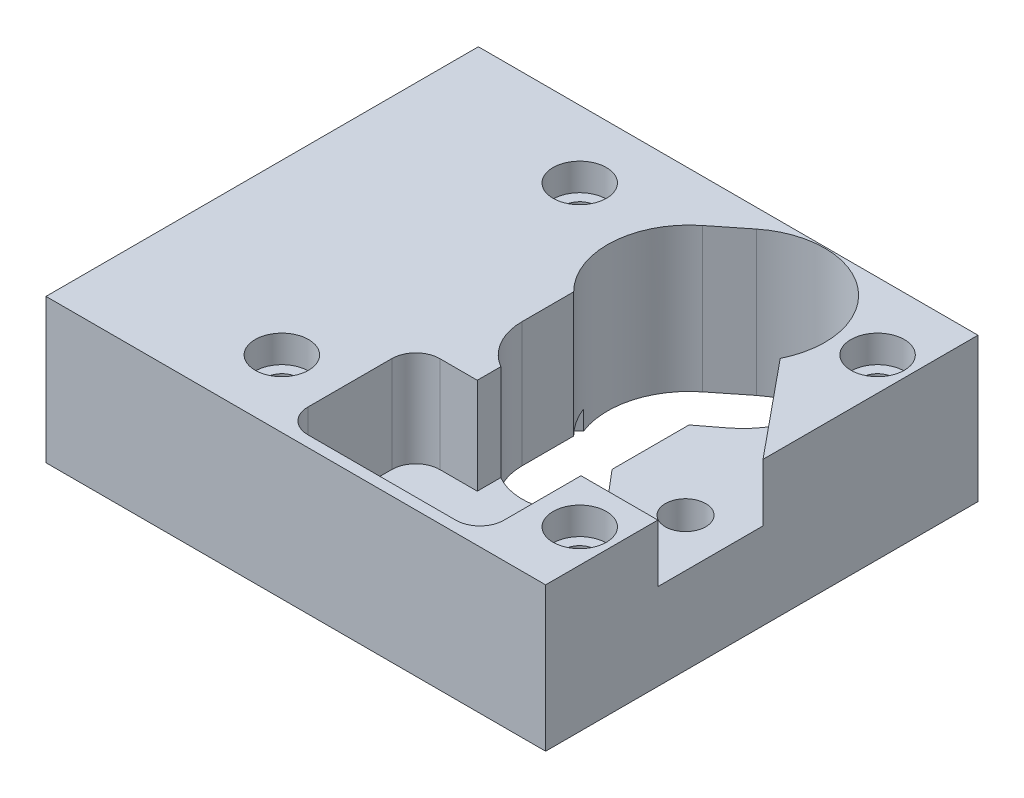
SolidWorks part; units mm, degrees
ref_plane "Front Plane" through (0, 0, 0) normal (0, 0, 1) x (1, 0, 0)
ref_plane "Top Plane" through (0, 0, 0) normal (0, 1, 0) x (1, 0, 0)
ref_plane "Right Plane" through (0, 0, 0) normal (1, 0, 0) x (0, 0, -1)
sketch "Sketch1" plane through (0, 0, 0) normal (0, 1, 0) x (1, 0, 0)
  line L1 (0, 0) -> (52, 0)
  line L2 (0, 0) -> (0, 45)
  line L3 (0, 45) -> (52, 45)
  line L4 (52, 0) -> (52, 45)
  dimension "D1" = 52
  dimension "D2" = 45
extrude "Boss-Extrude1" add sketch "Sketch1" along normal blind 15
sketch "Sketch2" plane through (0, 0, 0) normal (0, -1, 0) x (1, 0, 0)
  line L0 (33.0489, 0) -> (33.0489, -45) construction
  line L3 (52, -22.5) -> (0, -22.5) construction
  line L4 (52, 0) -> (52, -45) construction
  line L5 (0, -45) -> (0, 0) construction
  circle A0 centre (33.0489, -22.5) radius 11.5
  point P14 (17.5489, -7)
  point P15 (48.5489, -7)
  point P16 (48.5489, -38)
  point P17 (17.5489, -38)
  dimension "D1" = 23
  dimension "D2" = 15.5
  dimension "D3" = 15.5
extrude "Cut-Extrude1" cut sketch "Sketch2" against normal blind 2
ref_axis "Axis1" through (33.0489, 20.8863, -22.5) along (0, -1, 0)
hole_wizard "CBORE for #4 Socket Head Cap Screw1" positions "Sketch4" profile "Sketch5" counterbore size "#4" standard "Ansi Inch" end condition through all
sketch "Sketch4" plane through (0, 15, 0) normal (0, 1, 0) x (-1, 0, 0)
  point P0 (-48.5489, -38)
  point P1 (-48.5489, -7)
  point P3 (-17.5489, -7)
  point P5 (-17.5489, -38)
  dimension "D1" = 31
  dimension "D2" = 31
  dimension "D3" = 15.5
  dimension "D4" = 15.5
sketch "Sketch5" plane through (48.5489, 15, -38) normal (1, 0, 0) x (0, 0, 1)
  line L0 (0, 0) -> (0, 15)
  line L1 (0, 15) -> (1.6319, 15)
  line L3 (1.6319, 15) -> (1.632, 2.8448)
  line L4 (1.632, 2.8448) -> (2.7788, 2.8448)
  line L5 (2.7788, 2.8448) -> (2.7788, 0)
  line L7 (2.7788, 0) -> (0, 0)
  line L11 (0, -6.35) -> (0, 107.95) construction
  dimension "Thru Hole Dia." = 3.2639
  dimension "Thru Hole Depth" = 15
  dimension "C'Bore Dia." = 5.5575
  dimension "C'Bore Depth" = 2.8448
sketch "Layout sketch" plane through (0, 15, 0) normal (0, 1, 0) x (-1, 0, 0)
  line L0 (-5.4445, -22.5) -> (-55.1458, -22.5) construction
  line L1 (-33.0489, -33.89) -> (-47, -19.5594) construction
  line L2 (-52, 0) -> (-52, -45) construction
  line L3 (11.3783, -26.5) -> (-64.4521, -26.5) construction
  line L4 (-27.0489, -27.8692) -> (-27.0489, -22.5) construction
  line L6 (-39.0489, -22.5) -> (-39.0489, -27.8692) construction
  line L7 (-27.7584, -40.5429) -> (-30.8892, -43.0325) construction
  line L8 (-39.0489, -27.8692) -> (-41.3505, -29.6334) construction
  circle A0 centre (-33.0489, -22.5) radius 4 construction
  circle A1 centre (-33.0489, -33.89) radius 6.5 construction
  circle A2 centre (-47, -19.5594) radius 2.5 construction
  circle A3 centre (-33.0489, -33.89) radius 2.5 construction
  arc A4 (-27.0489, -27.8692) -> (-27.7584, -40.5429) centre (-33.0489, -33.89) cw construction
  arc A5 (-27.0489, -22.5) -> (-39.0489, -22.5) centre (-33.0489, -22.5) ccw construction
  arc A6 (-33.0489, -33.89) -> (-48.625, -39.4933) centre (-47, -19.5594) cw construction
  arc A7 (-30.8892, -43.0325) -> (-41.3505, -29.6334) centre (-36.1796, -36.3796) cw construction
  dimension "D1" = 8
  dimension "D2" = 13
  dimension "D3" = 5
  dimension "D4" = 5
  dimension "D5" = 2
  dimension "D6" = 2
  dimension "D8" = 2
  dimension "D7" = 2
  dimension "D10" = 20
  dimension "D12" = 0.89
  dimension "D9" = 4
  dimension "D11" = 5
sketch "Arm sketch" plane through (0, 15, 0) normal (0, 1, 0) x (1, 0, 0)
  line L0 (36.7672, 37.2328) -> (50.6672, 21.7711)
  line L3 (36.6105, 14.8843) -> (36.6105, 2.8045)
  line L4 (36.6105, 2.8045) -> (39.1105, 2.8045)
  line L5 (41.6105, 5.3045) -> (41.6105, 11.4363)
  line L6 (44.1105, 13.9363) -> (52.5715, 13.9363)
  line L7 (55.0562, 11.7121) -> (56.318, 0.3453)
  line L8 (56.318, 0.3453) -> (61.318, 0.3453)
  line L9 (61.318, 0.3453) -> (61.318, 15.5735)
  arc A0 (36.7672, 37.2328) -> (33.3407, 28.8985) centre (33.0489, 33.89) ccw
  arc A1 (33.3407, 28.8985) -> (36.6105, 14.8843) centre (33.7412, 21.6034) cw
  arc A2 (39.1105, 2.8045) -> (41.6105, 5.3045) centre (39.1105, 5.3045) ccw
  arc A3 (44.1105, 13.9363) -> (41.6105, 11.4363) centre (44.1105, 11.4363) ccw
  arc A4 (52.5715, 13.9363) -> (55.0562, 11.7121) centre (52.5715, 11.4363) cw
  arc A5 (50.6672, 21.7711) -> (58.8449, 18.0733) centre (58.9653, 29.231) ccw
  arc A6 (58.8449, 18.0733) -> (61.318, 15.5735) centre (58.818, 15.5735) cw
  dimension "D2" = 5
  dimension "D3" = 2.5
  dimension "D4" = 2.5
  dimension "D5" = 2.5
  dimension "D6" = 2.5
  dimension "D8" = 11.1583
  dimension "D1" = 5
  dimension "D7" = 5
sketch "Sketch8" plane through (0, 15, 0) normal (0, 1, 0) x (1, 0, 0)
  line L0 (27.0489, 22.5) -> (27.0489, 27.8692)
  line L1 (27.7584, 40.5429) -> (30.8892, 43.0325)
  line L2 (41.3505, 29.6334) -> (39.0489, 27.8692)
  line L3 (39.0489, 27.8692) -> (39.0489, 22.5)
  arc A0 (39.0489, 22.5) -> (27.0489, 22.5) centre (33.0489, 22.5) cw
  arc A1 (30.8892, 43.0325) -> (41.3505, 29.6334) centre (36.1796, 36.3796) cw
  arc A2 (27.7584, 40.5429) -> (27.0489, 27.8692) centre (33.0489, 33.89) ccw
extrude "Cut-Extrude3" cut sketch "Sketch8" against normal through all
sketch "Sketch11" plane through (0, 15, 0) normal (0, 1, 0) x (1, 0, 0)
  line L0 (23.6015, 12.3843) -> (23.6015, 3.6525)
  line L1 (26.1015, 1.1525) -> (41.5055, 1.1525)
  line L2 (44.0055, 3.6525) -> (44.0055, 13.0932)
  line L4 (39.0489, 19.863) -> (39.0489, 34.7253)
  line L7 (39.0489, 34.7253) -> (27.0489, 34.7253)
  line L8 (27.0489, 34.7253) -> (27.0489, 22.5)
  line L9 (26.1015, 14.8843) -> (30.0028, 14.8843)
  line L10 (30.0028, 14.8843) -> (30.0028, 17.3307)
  line L12 (39.0489, 22.5) -> (39.0489, 27.8692) construction
  line L13 (43.4134, 14.7087) -> (39.0489, 19.863)
  arc A1 (27.0489, 22.5) -> (30.0028, 17.3307) centre (33.0489, 22.5) ccw
  arc A2 (41.5055, 1.1525) -> (44.0055, 3.6525) centre (41.5055, 3.6525) ccw
  arc A3 (27.0489, 22.5) -> (39.0489, 22.5) centre (33.0489, 22.5) ccw construction
  arc A4 (23.6015, 3.6525) -> (26.1015, 1.1525) centre (26.1015, 3.6525) ccw
  arc A5 (23.6015, 12.3843) -> (26.1015, 14.8843) centre (26.1015, 12.3843) cw
  arc A6 (44.0055, 13.0932) -> (43.4134, 14.7087) centre (41.5055, 13.0932) ccw
  dimension "D1" = 2.5
  dimension "D2" = 2.5
  dimension "D3" = 2.5
  dimension "D4" = 2.5
extrude "Cut-Extrude4" cut sketch "Sketch11" against normal blind 10
sketch "Sketch12" plane through (0, 15, 0) normal (0, 1, 0) x (1, 0, 0)
  line L0 (43.5465, 11.677) -> (53.3517, 11.677)
  line L1 (53.3517, 11.677) -> (53.3517, 20.9784)
  line L2 (53.3517, 20.9784) -> (41.5225, 35.3895)
  line L3 (41.5225, 35.3895) -> (36.326, 27.3621)
  line L4 (36.326, 27.3621) -> (38.4832, 17.2859)
  line L5 (38.4832, 17.2859) -> (43.5465, 11.677)
extrude "Cut-Extrude5" cut sketch "Sketch12" against normal blind 6
hole_wizard "M5 Tapped Hole3" positions "Sketch18" profile "Sketch17" tap size "M5" standard "ISO" end condition through all
sketch "Sketch18" plane through (0, 15, 0) normal (0, 1, 0) x (-1, 0, 0)
  point P0 (-47, -19.5594)
sketch "Sketch17" plane through (47, 15, -19.5594) normal (1, 0, 0) x (0, 0, 1)
  line L0 (0, 0) -> (0, 15)
  line L1 (0, 15) -> (2.1, 15)
  line L2 (2.1, 15) -> (2.1, 0)
  line L5 (2.1, 0) -> (0, 0)
  line L11 (0, -6.35) -> (0, 107.95) construction
  dimension "Thru Tap Drill Dia." = 4.2
  dimension "Thru Tap Drill Depth" = 15
cosmetic thread "Hole Thread3" parameters "D2"=5
